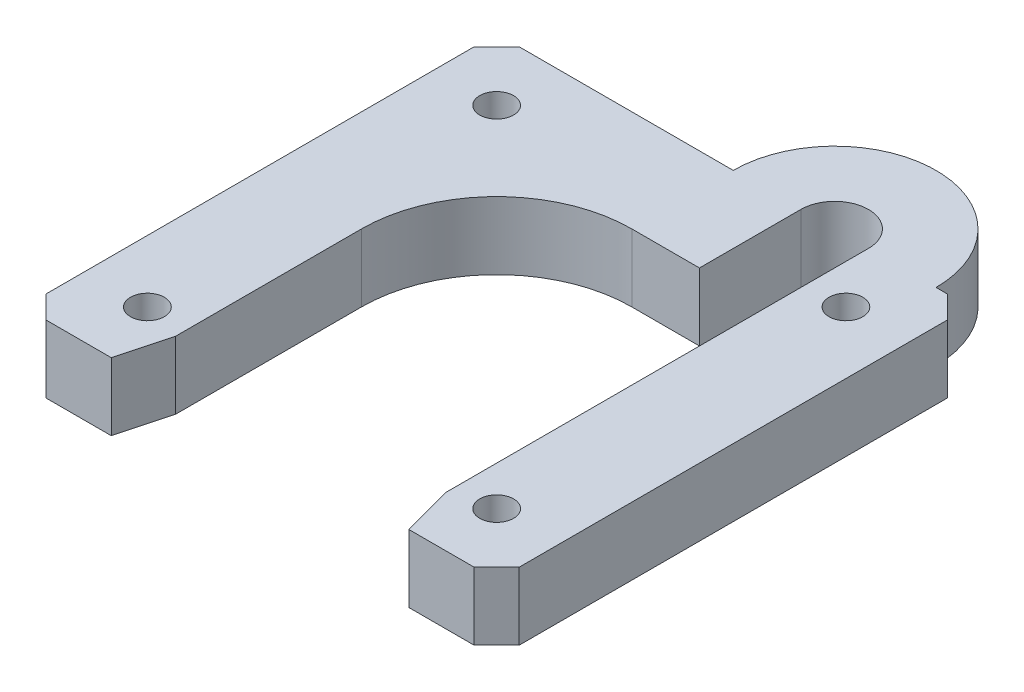
SolidWorks part; units mm, degrees
ref_plane "Front Plane" through (0, 0, 0) normal (0, 0, 1) x (1, 0, 0)
ref_plane "Top Plane" through (0, 0, 0) normal (0, 1, 0) x (1, 0, 0)
ref_plane "Right Plane" through (0, 0, 0) normal (1, 0, 0) x (0, 0, -1)
sketch "Sketch1" plane through (0, 0, 0) normal (0, 1, 0) x (1, 0, 0)
  line L1 (-21, -21) -> (21, -21)
  line L2 (-21, -21) -> (-21, 21)
  line L3 (-21, 21) -> (21, 21)
  line L4 (21, -21) -> (21, 21)
  line L5 (-21, -21) -> (21, 21) construction
  line L6 (-21, 21) -> (21, -21) construction
  line L7 (-15.5, 15.5) -> (15.5, 15.5) construction
  line L8 (-15.5, 15.5) -> (-15.5, -15.5) construction
  line L9 (-15.5, -15.5) -> (15.5, -15.5) construction
  line L10 (15.5, 15.5) -> (15.5, -15.5) construction
  circle A0 centre (0, 0) radius 12
  circle A1 centre (-15.5, 15.5) radius 1.5
  circle A2 centre (15.5, 15.5) radius 1.5
  circle A3 centre (15.5, -15.5) radius 1.5
  circle A4 centre (-15.5, -15.5) radius 1.5
  point P0 (0, 0)
  dimension "D2" = 24
  dimension "D3" = 3
  dimension "D1" = 42
  dimension "D4" = 31
extrude "Boss-Extrude1" add sketch "Sketch1" along normal blind 6
chamfer "Chamfer1" distance 2 angle 45 4 edges at (-21, 3, -21) (21, 3, -21) (21, 3, 21) (-21, 3, 21)
sketch "Sketch2" plane through (0, 6, 0) normal (0, 1, 0) x (1, 0, 0)
  line L0 (-12, 0) -> (-12, -21)
  line L1 (-19, -21) -> (19, -21) construction
  line L2 (-12, -21) -> (12, -21)
  line L3 (12, -21) -> (12, 0)
  line L4 (12, 0) -> (-12, 0)
  circle A0 centre (0, 0) radius 12 construction
extrude "Cut-Extrude1" cut sketch "Sketch2" against normal through all
chamfer "Chamfer2" distance 4.5 angle 15 2 edges at (12, 3, 21) (-12, 3, 21) first distance on face at (12, 3, 10.5) first distance on face at (-12, 3, 10.5)
sketch "Sketch3" plane through (0, 6, 0) normal (0, 1, 0) x (1, 0, 0)
  line L0 (12, 0) -> (12, 21) construction
  line L1 (19, 21) -> (-19, 21) construction
  line L2 (6, 21) -> (6, 12) construction
  line L3 (0, 21) -> (0, 12) construction
  line L4 (0, 12) -> (6, 12) construction
  line L5 (0, 21) -> (6, 21)
  line L6 (18, 21) -> (12, 21)
  arc A0 (12, 21) -> (6, 21) centre (9, 21) ccw
  arc A1 (0, 21) -> (18, 21) centre (9, 21) cw
  arc A3 (12, 0) -> (-12, 0) centre (0, 0) ccw construction
  dimension "D1" = 6
  dimension "D2" = 3
extrude "Boss-Extrude2" add sketch "Sketch3" against normal up to surface (6 mm away) up to face at (0, 0, 4.5)
sketch "Sketch4" plane through (0, 6, 6) normal (0, 1, 0) x (1, 0, 0)
  line L0 (12, 6) -> (12, 27)
  line L2 (6, 27) -> (6, 18)
  line L3 (-3.575, 6) -> (3.575, 6) construction
  line L4 (0, 18) -> (6, 18)
  line L5 (0, 18) -> (0, 6)
  line L6 (0, 6) -> (12, 6)
  line L7 (0, 2.425) -> (0, 9.575) construction
  arc A0 (12, 27) -> (6, 27) centre (9, 27) ccw
  arc A3 (12, 27) -> (6, 27) centre (9, 27) ccw construction
  arc A4 (12, 6) -> (-12, 6) centre (0, 6) ccw construction
  dimension "D2" = 3
extrude "Cut-Extrude2" cut sketch "Sketch4" against normal through all
equation "\"M3_d\"= \"M3_d_laser@troublemaker.Assembly\""
equation "\"housing_t\"= \"housing_t_glob@troublemaker.Assembly\""
equation "\"D3@Sketch1\"=\"M3_d\""
equation "\"D1@Boss-Extrude1\"=\"housing_t\""
